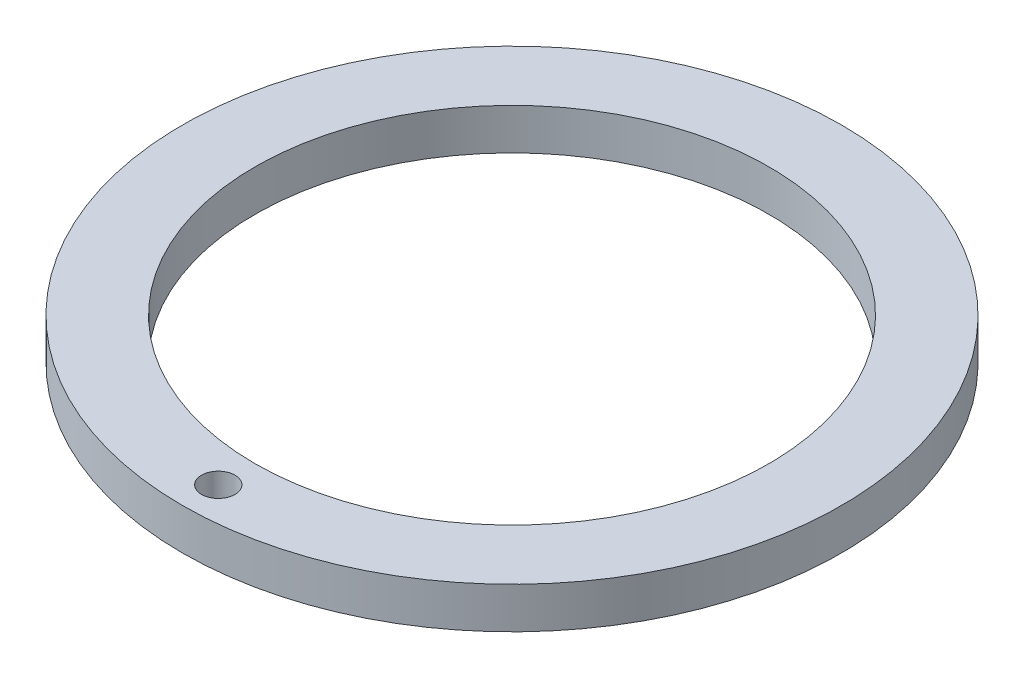
SolidWorks part; units mm, degrees
material "C-Glass Fiber"
ref_plane "Front Plane" through (0, 0, 0) normal (0, 0, 1) x (1, 0, 0)
ref_plane "Top Plane" through (0, 0, 0) normal (0, 1, 0) x (1, 0, 0)
ref_plane "Right Plane" through (0, 0, 0) normal (1, 0, 0) x (0, 0, -1)
sketch "Sketch1" plane through (0, 0, 0) normal (0, 1, 0) x (1, 0, 0)
  circle A0 centre (0, 0) radius 39.624
  circle A1 centre (0, 0) radius 50.8
  dimension "D1" = 101.6
  dimension "D2" = 79.248
extrude "Ring Extrusion" add sketch "Sketch1" along normal blind 6.35 contours A1 | A0
sketch "Sketch2" plane through (0, 0, 0) normal (0, 1, 0) x (1, 0, 0)
  circle A0 centre (0, -45.2755) radius 2.5797
  circle A2 centre (0, 0) radius 45.2755 construction
  circle A5 centre (0, 0) radius 50.8 construction
  circle A6 centre (0, 0) radius 39.624 construction
  circle A7 centre (0, 0) radius 50.8 construction
  circle A8 centre (0, 0) radius 39.624 construction
  dimension "D1" = 5.1594
  dimension "D2" = 79.248
  dimension "D3" = 101.6
  dimension "D4" = 90.551
extrude "Conduit Hole" cut sketch "Sketch2" along normal through all
equation "\"D4@Sketch2\"=(\"D2@Sketch2\"+\"D3@Sketch2\")/2"
